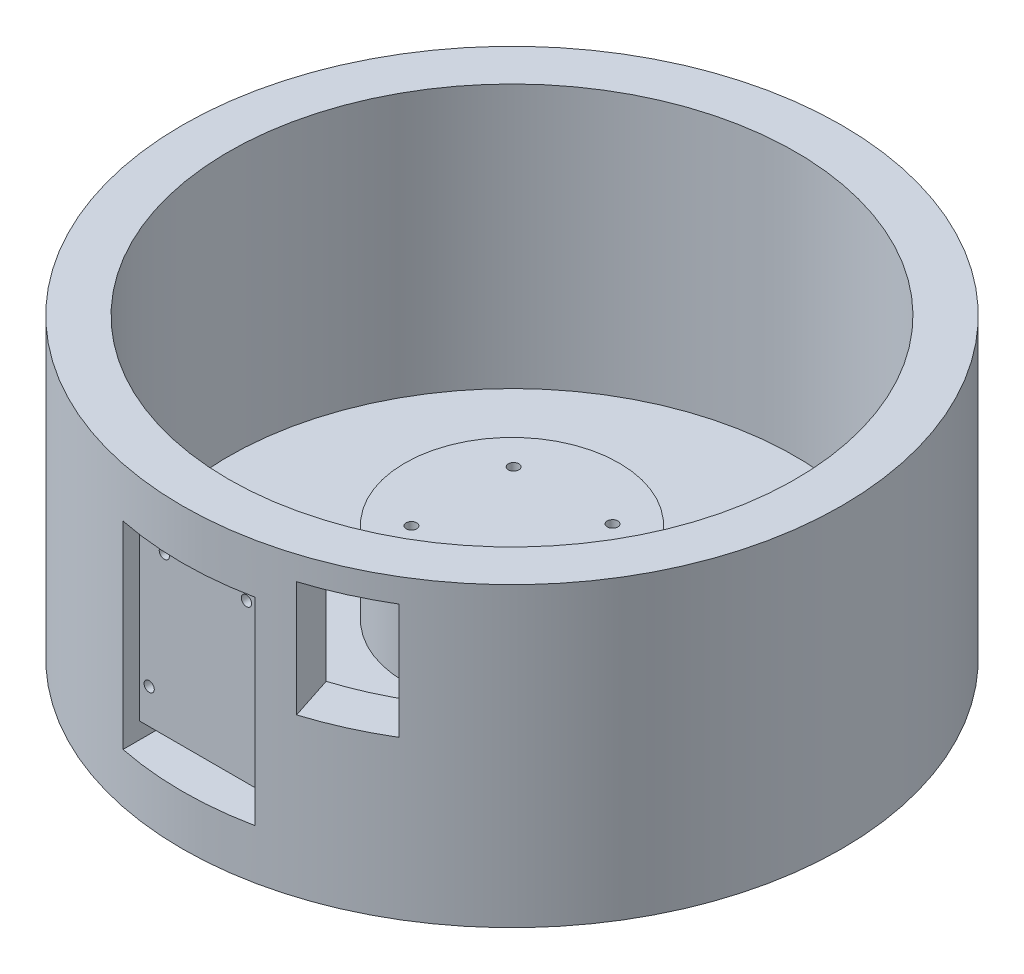
SolidWorks part; units mm, degrees
material "ABS"
ref_plane "Front Plane" through (0, 0, 0) normal (0, 0, 1) x (1, 0, 0)
ref_plane "Top Plane" through (0, 0, 0) normal (0, 1, 0) x (1, 0, 0)
ref_plane "Right Plane" through (0, 0, 0) normal (1, 0, 0) x (0, 0, -1)
sketch "Sketch1" plane through (0, 0, 0) normal (0, 1, 0) x (1, 0, 0)
  circle A1 centre (0, 0) radius 100
extrude "Boss-Extrude3" add sketch "Sketch1" along normal blind 90
ref_plane "Plane1" through (0, 0, 105) normal (0, 0, 1) x (1, 0, 0)
sketch "Sketch4" plane through (0, 0, 105) normal (0, 0, 1) x (1, 0, 0)
  line L26 (-20, 75) -> (20, 75)
  line L27 (-20, 75) -> (-20, 15)
  line L28 (-20, 15) -> (20, 15)
  line L29 (20, 75) -> (20, 15)
  line L30 (-20, 75) -> (20, 15) construction
  line L31 (-20, 15) -> (20, 75) construction
  point P5 (0, 45)
  dimension "D1" = 60
  dimension "D2" = 40
  dimension "D3" = 45
extrude "Cut-Extrude2" cut sketch "Sketch4" along normal blind 26 and the other way blind 12
sketch "Sketch12" plane through (0, 0, 0) normal (0, -1, 0) x (1, 0, 0)
  circle A1 centre (0, 0) radius 100
  circle A2 centre (0, 0) radius 100
  dimension "D1" = 0
extrude "Boss-Extrude4" add sketch "Sketch12" along normal blind 0.1
sketch "Sketch13" plane through (0, 90, 0) normal (0, 1, 0) x (1, 0, 0)
  circle A0 centre (0, 0) radius 86
extrude "Cut-Extrude8" cut sketch "Sketch13" against normal blind 80 contours A0
sketch "Sketch18" plane through (0, 10, 0) normal (0, 1, 0) x (1, 0, 0)
  circle A0 centre (0, 0) radius 32.5
  dimension "D1" = 65
extrude "Boss-Extrude5" add sketch "Sketch18" along normal blind 25
sketch "Sketch16" plane through (0, -0.1, 0) normal (0, -1, 0) x (1, 0, 0)
  line L0 (0, 0) -> (-8.9936, 0) construction
  line L1 (0, 0) -> (0, 9.8047) construction
  circle A2 centre (-15, 15.5) radius 1.6
  circle A5 centre (15, 15.5) radius 1.6
  circle A6 centre (15, -15.5) radius 1.6
  circle A7 centre (-15, -15.5) radius 1.6
  dimension "D3" = 3.2
  dimension "D1" = 15.5
  dimension "D2" = 15
extrude "Cut-Extrude11" cut sketch "Sketch16" against normal through all
sketch "Sketch17" plane through (0, -0.1, 0) normal (0, -1, 0) x (1, 0, 0)
  circle A0 centre (-15, 15.5) radius 3
  circle A1 centre (15, 15.5) radius 3
  circle A2 centre (-15, -15.5) radius 3
  circle A3 centre (15, -15.5) radius 3
  dimension "D1" = 6
  dimension "D2" = 6
  dimension "D3" = 6
  dimension "D4" = 6
extrude "Cut-Extrude12" cut sketch "Sketch17" against normal blind 30
sketch "Sketch19" plane through (0, -0.1, 0) normal (0, -1, 0) x (1, 0, 0)
  circle A0 centre (0, 0) radius 30
  dimension "D1" = 60
extrude "Cut-Extrude13" cut sketch "Sketch19" against normal blind 25 contours A0
sketch "Sketch20" plane through (0, 0, 93) normal (0, 0, 1) x (1, 0, 0)
  line L0 (20, 75) -> (20, 15) construction
  line L1 (-20, 15) -> (20, 15)
  line L2 (-20, 15) -> (-20, 20)
  line L3 (-20, 20) -> (20, 20)
  line L4 (20, 15) -> (20, 20)
  dimension "D1" = 5
extrude "Cut-Extrude14" cut sketch "Sketch20" against normal blind 25
sketch "Sketch21" plane through (0, 0, 93) normal (0, 0, 1) x (1, 0, 0)
  line L0 (20, 75) -> (-20, 75) construction
  circle A0 centre (12.45, 67.8) radius 1.55
  circle A1 centre (-12.45, 67.8) radius 1.55
  circle A2 centre (-17.05, 30.54) radius 1.55
  circle A3 centre (17.05, 30.54) radius 1.55
  dimension "D3" = 3.1
  dimension "D4" = 3.1
  dimension "D9" = 3.1
  dimension "D10" = 3.1
  dimension "D1" = 12.45
  dimension "D2" = 24.9
  dimension "D5" = 7.2
  dimension "D6" = 7.2
  dimension "D7" = 17.05
  dimension "D8" = 17.05
  dimension "D11" = 37.26
  dimension "D12" = 37.26
extrude "Cut-Extrude15" cut sketch "Sketch21" against normal blind 25
ref_plane "Plane2" through (22.2041, 47.7941, -296.4042) normal (0, 1, 0) x (1, 0, 0)
sketch "Sketch22" plane through (22.2041, 47.7941, -296.4042) normal (0, 1, 0) x (1, 0, 0)
  line L0 (-6.7919, -346.9591) -> (12.405, -405.7625)
  line L1 (-6.7919, -346.9591) -> (3.9537, -342.2121)
  line L2 (3.9537, -342.2121) -> (37.058, -394.3842)
  line L3 (12.405, -405.7625) -> (37.058, -394.3842)
extrude "Cut-Extrude16" cut sketch "Sketch22" along normal blind 35
